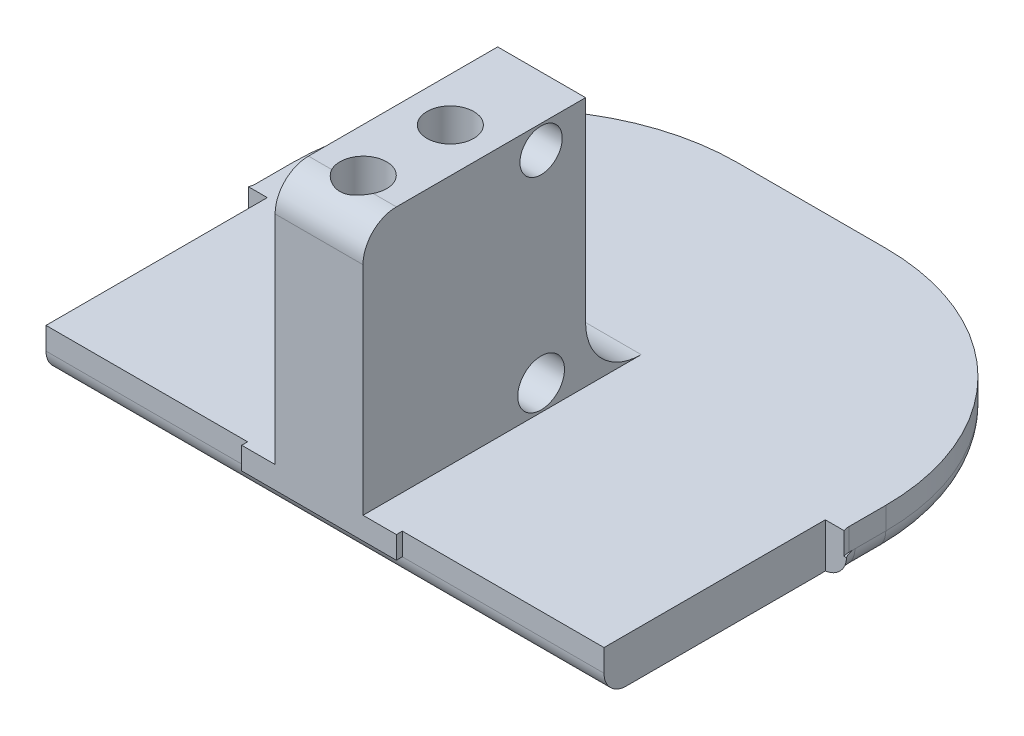
SolidWorks part; units mm, degrees
ref_plane "Alzado" through (0, 0, 0) normal (0, 0, 1) x (1, 0, 0)
ref_plane "Planta" through (0, 0, 0) normal (0, 1, 0) x (1, 0, 0)
ref_plane "Vista lateral" through (0, 0, 0) normal (1, 0, 0) x (0, 0, -1)
sketch "Croquis1" plane through (0, 0, 0) normal (0, 1, 0) x (1, 0, 0)
  line L5 (0, 34.2669) -> (0, 18.57) construction
  line L6 (-31.5, -9.4645) -> (31.5, -9.4645)
  line L8 (-26.6601, 14.2669) -> (-26.6601, 10.9645)
  line L9 (30, 9.4645) -> (28.1601, 9.4645)
  line L11 (26.6601, 14.2669) -> (26.6601, 10.9645)
  line L12 (-31.5, -9.4645) -> (-31.5, 7.9645)
  line L13 (-30, 9.4645) -> (-28.1601, 9.4645)
  line L14 (31.5, -9.4645) -> (31.5, 7.9645)
  line L15 (-31.5, -9.4645) -> (30.7773, 9.2474) construction
  line L16 (-31.5, 9.4645) -> (31.5, -9.4645) construction
  line L17 (0, 0) -> (0, 1.6095) construction
  line L19 (-6.6601, 34.2669) -> (6.6601, 34.2669)
  arc A2 (-26.6601, 14.2669) -> (-6.6601, 34.2669) centre (-6.6601, 14.2669) cw
  arc A3 (-26.6601, 10.9645) -> (-28.1601, 9.4645) centre (-28.1601, 10.9645) cw
  arc A4 (-31.5, 7.9645) -> (-30, 9.4645) centre (-30, 7.9645) cw
  arc A5 (31.5, 7.9645) -> (30, 9.4645) centre (30, 7.9645) ccw
  arc A6 (26.6601, 10.9645) -> (28.1601, 9.4645) centre (28.1601, 10.9645) ccw
  arc A7 (26.6601, 14.2669) -> (6.6601, 34.2669) centre (6.6601, 14.2669) ccw
  point P0 (0, 0)
  point P1 (0, 0)
  point P19 (25.5, 34.8024)
  point P22 (-25.5, 34.8024)
  point P33 (25.5, 34.8024)
  dimension "D3" = 1.5
  dimension "D2" = 20
  dimension "D1" = 63
extrude "Saliente-Extruir1" add sketch "Croquis1" along normal blind 2
sketch "Croquis2" plane through (0, 0, 0) normal (0, 1, 0) x (1, 0, 0)
  line L1 (-6.95, 10) -> (6.95, 10)
  line L2 (-6.95, 10) -> (-6.95, -10)
  line L3 (-6.95, -10) -> (6.95, -10)
  line L4 (6.95, 10) -> (6.95, -10)
  line L5 (-6.95, 10) -> (6.95, -10) construction
  line L6 (-6.95, -10) -> (6.95, 10) construction
  point P0 (0, 0)
  dimension "D1" = 13.9
extrude "Saliente-Extruir2" add sketch "Croquis2" along normal blind 24.5
sketch "Croquis3" plane through (0, 2, 0) normal (0, 1, 0) x (1, 0, 0)
  line L5 (-31.5, 7.9645) -> (-31.5, -9.4645) construction
  line L6 (0, 34.2669) -> (0, 0)
  line L16 (-31.5, 10.2854) -> (-31.5, -0.75)
  line L26 (31.5, -2.75) -> (31.5, 10.2854)
  line L27 (6.6601, 34.2669) -> (-6.6601, 34.2669) construction
  line L28 (31.5, -2.75) -> (25.6, -2.75)
  line L29 (31.5, 10.2854) -> (30.6, 10.2854)
  line L30 (25.6, -2.75) -> (25.6, 10.2854)
  line L31 (25.6, 10.2854) -> (30.6, 10.2854)
  line L33 (25.5, -11.1976) -> (25.5, 0.8024) construction
  line L39 (-25.6, -0.75) -> (-25.6, 10.2854)
  line L40 (-25.5, 0.8024) -> (-25.5, 34.8024) construction
  line L41 (-31.5, 10.2854) -> (-25.6, 10.2854)
  line L42 (5, 10.2854) -> (0, 10.2854)
  line L43 (-25.6, -0.75) -> (-25.6, -2.75)
  line L44 (-25.6, -2.75) -> (-31.5, -2.75)
  line L45 (-31.5, -2.75) -> (-31.5, -0.75)
  dimension "D1" = 0.1
  dimension "D2" = 5
  dimension "D3" = 0.1
  dimension "D4" = 13.0354
extrude "Saliente-Extruir3" add sketch "Croquis3" along normal blind 22.5
sketch "Croquis5" plane through (0, 24.5, 0) normal (0, 1, 0) x (1, 0, 0)
  line L1 (0, 0) -> (0, -1.2356) construction
  circle A0 centre (0, 1.7983) radius 2.1
  circle A1 centre (0, -6.0269) radius 2.1
  circle A6 centre (-28.55, 1.7983) radius 2.1
  circle A7 centre (28.55, 1.7983) radius 2.1
  dimension "D1" = 4.2
  dimension "D3" = 4.2
  dimension "D4" = 4.2
  dimension "D2" = 4.2
  dimension "D5" = 2.95
  dimension "D6" = 2.95
extrude "Cortar-Extruir2" cut sketch "Croquis5" against normal blind 20.5
sketch "Croquis16" plane through (0, 24.5, 0) normal (0, 1, 0) x (1, 0, 0)
  line L0 (6.95, 17.2358) -> (6.95, -16.6947)
  line L1 (6.95, -9.4645) -> (6.95, 10) construction
  line L2 (6.95, -16.6947) -> (3.95, -16.6947)
  line L3 (3.95, -16.6947) -> (3.95, 17.2358)
  line L4 (3.95, 17.2358) -> (6.95, 17.2358)
  line L5 (0, 0) -> (0, -1.6484)
  line L6 (-3.95, 17.2358) -> (-6.95, 17.2358)
  line L7 (-6.95, -16.6947) -> (-3.95, -16.6947)
  line L8 (-6.95, 17.2358) -> (-6.95, -16.6947)
  line L9 (-3.95, -16.6947) -> (-3.95, 17.2358)
  dimension "D1" = 3
extrude "Cortar-Extruir8" cut sketch "Croquis16" against normal up to surface (22.5 mm away)
sketch "Croquis4" plane through (-25.5, 0, 0) normal (-1, 0, 0) x (0, 0, 1)
  circle A0 centre (-6.0024, 4.3) radius 1.6
  circle A1 centre (-6.0024, 22.4) radius 1.6
  dimension "D1" = 3.2
  dimension "D2" = 3.2
extrude "Cortar-Extruir1" cut sketch "Croquis4" against normal blind 65.5 and the other way blind 27
fillet "Redondeo1" radius 3 2 edges at (28.55, 2, 2.75) (0, 24.5, 10)
fillet "Redondeo2" radius 5 1 edges at (0, 2, -10)
sketch "Croquis7" plane through (0, 24.5, 0) normal (0, 1, 0) x (1, 0, 0)
  line L0 (6.95, 6.0024) -> (-6.95, 6.0024) construction
  line L1 (6.95, 4.4024) -> (6.95, 7.6024) construction
  line L2 (-6.95, 7.6024) -> (-6.95, 4.4024) construction
sketch "Croquis8" plane through (0, 0, 0) normal (1, 0, 0) x (0, 0, -1)
  line L7 (2.7524, 22.4) -> (4.3774, 19.5854)
  line L8 (4.3774, 19.5854) -> (7.6274, 19.5854)
  line L9 (7.6274, 19.5854) -> (9.2524, 22.4)
  line L10 (9.2524, 22.4) -> (7.6274, 25.2146)
  line L11 (7.6274, 25.2146) -> (4.3774, 25.2146)
  line L12 (4.3774, 25.2146) -> (2.7524, 22.4)
  circle A0 centre (6.0024, 22.4) radius 2.8146 construction
  dimension "D1" = 6.5
sketch "Croquis9" plane through (0, 0, 0) normal (1, 0, 0) x (0, 0, -1)
  line L1 (2.7524, 22.4) -> (4.3774, 19.5854)
  line L2 (4.3774, 19.5854) -> (7.6274, 19.5854)
  line L3 (7.6274, 19.5854) -> (9.2524, 22.4)
  line L4 (9.2524, 22.4) -> (7.6274, 25.2146)
  line L5 (7.6274, 25.2146) -> (4.3774, 25.2146)
  line L6 (4.3774, 25.2146) -> (2.7524, 22.4)
  circle A0 centre (6.0024, 22.4) radius 2.8146 construction
  dimension "D1" = 6.5
sketch "Croquis10" plane through (0, 0, 0) normal (1, 0, 0) x (0, 0, -1)
  line L1 (6.0024, 7.55) -> (3.1878, 5.925)
  line L2 (3.1878, 5.925) -> (3.1878, 2.675)
  line L3 (3.1878, 2.675) -> (6.0024, 1.05)
  line L4 (6.0024, 1.05) -> (8.8169, 2.675)
  line L5 (8.8169, 2.675) -> (8.8169, 5.925)
  line L6 (8.8169, 5.925) -> (6.0024, 7.55)
  circle A0 centre (6.0024, 4.3) radius 2.8146 construction
  dimension "D1" = 6.5
sketch "Croquis11" plane through (0, 0, 0) normal (1, 0, 0) x (0, 0, -1)
  line L1 (2.7524, 4.3) -> (4.3774, 1.4854)
  line L2 (4.3774, 1.4854) -> (7.6274, 1.4854)
  line L3 (7.6274, 1.4854) -> (9.2524, 4.3)
  line L4 (9.2524, 4.3) -> (7.6274, 7.1146)
  line L5 (7.6274, 7.1146) -> (4.3774, 7.1146)
  line L6 (4.3774, 7.1146) -> (2.7524, 4.3)
  circle A0 centre (6.0024, 4.3) radius 2.8146 construction
  dimension "D1" = 6.5
sketch "Croquis15" plane through (0, 0, 0) normal (0, -1, 0) x (1, 0, 0)
  line L6 (-31.5, 9.4645) -> (31.5, 9.4645)
  line L7 (31.5, 9.4645) -> (31.5, -7.4891)
  line L8 (29.5, -9.4891) -> (28.6601, -9.4891)
  line L9 (26.6601, -11.4891) -> (26.6601, -14.2669)
  line L10 (6.6601, -34.2669) -> (1.1376, -34.2669)
  line L11 (6.6601, -34.2669) -> (-6.6601, -34.2669) construction
  line L12 (0, 9.4645) -> (0, 4.258) construction
  line L13 (-6.6601, -34.2669) -> (-1.1376, -34.2669)
  line L14 (-26.6601, -11.4891) -> (-26.6601, -14.2669)
  line L15 (-29.5, -9.4891) -> (-28.6601, -9.4891)
  line L16 (-31.5, 9.4645) -> (-31.5, -7.4891)
  line L17 (1.1376, -34.2669) -> (-1.1376, -34.2669)
  arc A0 (28.6601, -9.4891) -> (26.6601, -11.4891) centre (28.6601, -11.4891) ccw
  arc A1 (31.5, -7.4891) -> (29.5, -9.4891) centre (29.5, -7.4891) cw
  arc A2 (26.6601, -14.2669) -> (6.6601, -34.2669) centre (6.6601, -14.2669) cw
  arc A3 (-26.6601, -14.2669) -> (-6.6601, -34.2669) centre (-6.6601, -14.2669) ccw
  arc A4 (-31.5, -7.4891) -> (-29.5, -9.4891) centre (-29.5, -7.4891) ccw
  arc A5 (-28.6601, -9.4891) -> (-26.6601, -11.4891) centre (-28.6601, -11.4891) cw
  dimension "D1" = 2
  dimension "D2" = 20
extrude "Saliente-Extruir5" add sketch "Croquis15" along normal blind 2
sketch "Croquis13" plane through (0, 0, 0) normal (0, -1, 0) x (1, 0, 0)
  line L0 (6.95, -6.0024) -> (-6.95, -6.0024) construction
  line L1 (-5, -2.7524) -> (5, -2.7524)
  line L2 (-5, -2.7524) -> (-5, -9.2524)
  line L3 (-5, -9.2524) -> (5, -9.2524)
  line L4 (5, -2.7524) -> (5, -9.2524)
  line L5 (-5, -2.7524) -> (5, -9.2524) construction
  line L6 (-5, -9.2524) -> (5, -2.7524) construction
  point P0 (0, -6.0024)
  dimension "D1" = 6.5
  dimension "D2" = 10
fillet "Redondeo6" radius 2 13 edges at (-31.5, -2, 0.9877) (-30.9142, -2, -8.9033) (-29.0801, -2, -9.4891) (-27.2459, -2, -10.0749) (-26.6601, -2, -12.878) (-20.8022, -2, -28.409) (0, -2, -34.2669) (20.8022, -2, -28.409) (26.6601, -2, -12.878) (27.2459, -2, -10.0749) (29.0801, -2, -9.4891) (30.9142, -2, -8.9033) (31.5, -2, 0.9877)
fillet "Redondeo7" radius 2 5 edges at (31.5, 1, 9.4645) (30.9142, -1.4142, 9.4645) (-31.5, 1, 9.4645) (-30.9142, -1.4142, 9.4645) (0, -2, 9.4645)
sketch "Croquis17" plane through (0, 0, 0) normal (1, 0, 0) x (0, 0, -1)
  circle A0 centre (6.0024, 4.3) radius 2.1
  dimension "D1" = 4.2
extrude "Cortar-Extruir9" cut sketch "Croquis17" against normal mid plane 20
sketch "Croquis18" plane through (0, 0, 0) normal (1, 0, 0) x (0, 0, -1)
  circle A0 centre (6.0024, 22.4) radius 1.9
  dimension "D1" = 3.8
extrude "Cortar-Extruir14" cut sketch "Croquis18" against normal blind 10 and the other way blind 11
sketch "Croquis19" plane through (31.5, 0, 0) normal (1, 0, 0) x (0, 0, -1)
  circle A0 centre (25.1798, 14.0455) radius 18.5
  dimension "D1" = 37
extrude "Cortar-Extruir15" cut sketch "Croquis19" against normal blind 3.5
sketch "Croquis20" plane through (28, 0, 0) normal (1, 0, 0) x (0, 0, -1)
  circle A0 centre (25.1798, 14.0455) radius 18.5
extrude "Cortar-Extruir16" cut sketch "Croquis20" along normal blind 3.5 from surface at -59.5 starting at face at (-31.5, 4.3, -7.6024)
sketch "Croquis21" plane through (0, 2, 0) normal (0, 1, 0) x (1, 0, 0)
  line L0 (-29.5, -9.4645) -> (-6.95, -9.4645) construction
  line L1 (-25.0706, -9.4645) -> (-32.4684, -9.4645)
  line L2 (-25.0706, -9.4645) -> (-25.0706, 10.4208)
  line L3 (-25.0706, 10.4208) -> (-32.4684, 10.4208)
  line L4 (-32.4684, -9.4645) -> (-32.4684, 10.4208)
  line L5 (0, 0) -> (0, -15.9655) construction
  line L6 (32.4684, -9.4645) -> (32.4684, 10.4208)
  line L7 (25.0706, 10.4208) -> (32.4684, 10.4208)
  line L8 (25.0706, -9.4645) -> (25.0706, 10.4208)
  line L9 (25.0706, -9.4645) -> (32.4684, -9.4645)
extrude "Cortar-Extruir17" cut sketch "Croquis21" along normal blind 47 and the other way blind 86
